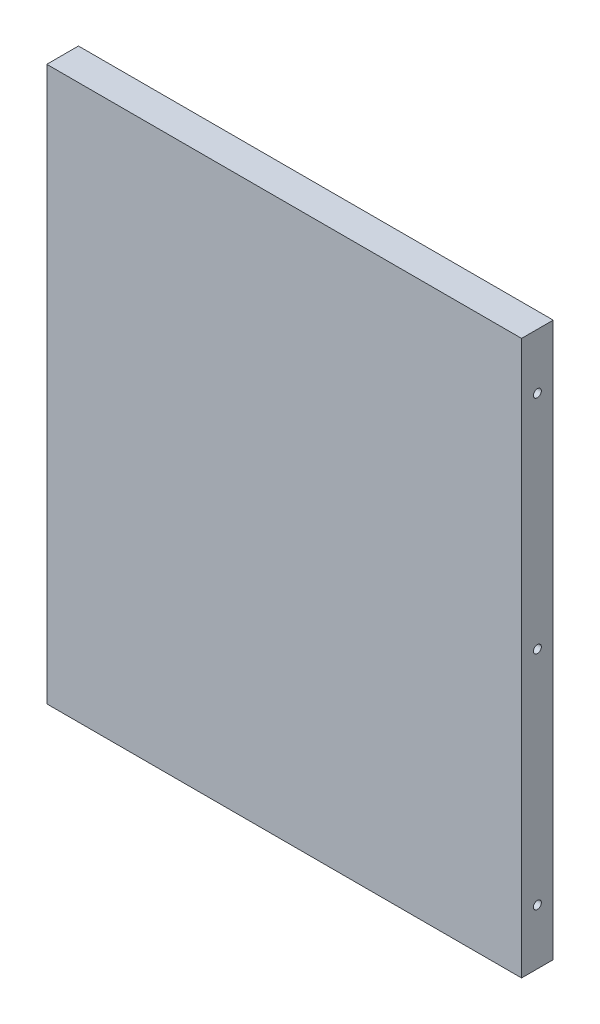
SolidWorks part; units mm, degrees
material "3.0205 (EN-AW 1200)"
ref_plane "Ebene vorne" through (0, 0, 0) normal (0, 0, 1) x (1, 0, 0)
ref_plane "Ebene oben" through (0, 0, 0) normal (0, 1, 0) x (1, 0, 0)
ref_plane "Ebene rechts" through (0, 0, 0) normal (1, 0, 0) x (0, 0, -1)
sketch "Skizze1" plane through (0, 0, 0) normal (0, 0, 1) x (1, 0, 0)
  line L1 (-84.7009, 65.5769) -> (65.2991, 65.5769)
  line L2 (-84.7009, 65.5769) -> (-84.7009, -109.4231)
  line L3 (-84.7009, -109.4231) -> (65.2991, -109.4231)
  line L4 (65.2991, 65.5769) -> (65.2991, -109.4231)
  dimension "D1" = 150
  dimension "D2" = 175
extrude "Aufsatz-Linear austragen1" add sketch "Skizze1" along normal blind 10
sketch "Skizze2" plane through (-84.7009, 0, 0) normal (-1, 0, 0) x (0, 0, 1)
  line L0 (0, -21.9231) -> (10, -21.9231) construction
  line L1 (0, 65.5769) -> (0, -109.4231) construction
  line L2 (10, 65.5769) -> (10, -109.4231) construction
  line L3 (5, -91.9231) -> (5, -21.9231) construction
  line L4 (5, -21.9231) -> (5, 48.0769) construction
  circle A0 centre (5, 48.0769) radius 1.25
  circle A1 centre (5, -21.9231) radius 1.25
  circle A3 centre (5, -91.9231) radius 1.25
  point P11 (5, -21.9231)
  dimension "D2" = 2.5
  dimension "D1" = 70
extrude "Schnitt-Linear austragen1" cut sketch "Skizze2" against normal blind 5
sketch "Skizze3" plane through (65.2991, 0, 0) normal (1, 0, 0) x (0, 0, -1)
  line L0 (-10, -21.9231) -> (0, -21.9231) construction
  line L1 (-5, -91.9231) -> (-5, -21.9231) construction
  line L2 (-5, -21.9231) -> (-5, 48.0769) construction
  line L4 (0, -109.4231) -> (0, 65.5769) construction
  line L5 (-10, -109.4231) -> (-10, 65.5769) construction
  circle A0 centre (-5, 48.0769) radius 1.25
  circle A1 centre (-5, -21.9231) radius 1.25
  circle A3 centre (-5, -91.9231) radius 1.25
  point P7 (-5, -21.9231)
  dimension "D2" = 2.5
  dimension "D1" = 70
extrude "Schnitt-Linear austragen2" cut sketch "Skizze3" against normal blind 5
